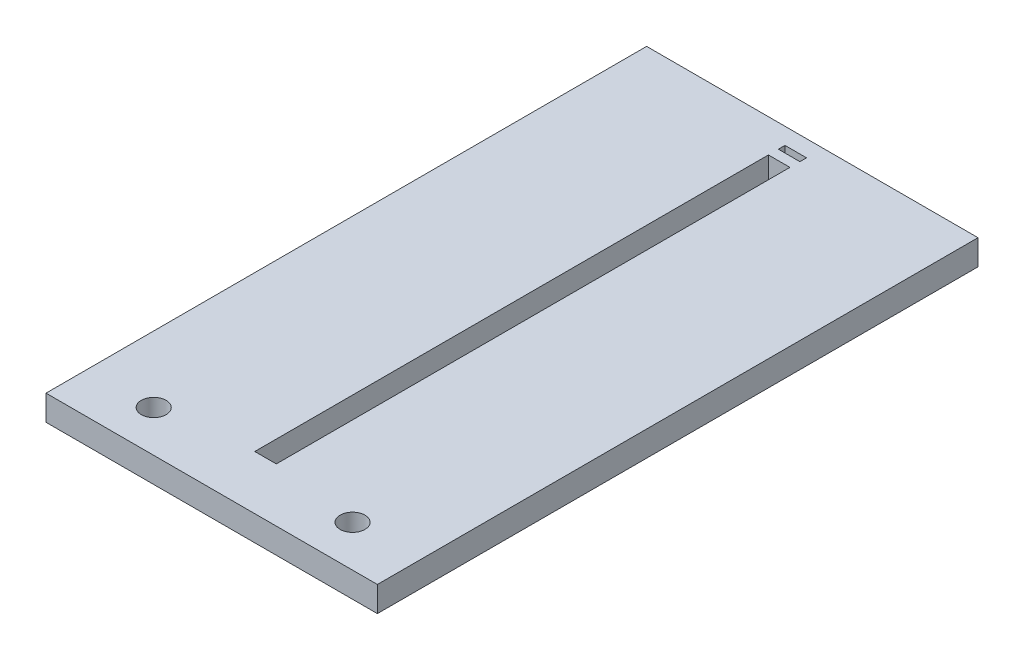
SolidWorks part; units mm, degrees
ref_plane "Front Plane" through (0, 0, 0) normal (0, 0, 1) x (1, 0, 0)
ref_plane "Top Plane" through (0, 0, 0) normal (0, 1, 0) x (1, 0, 0)
ref_plane "Right Plane" through (0, 0, 0) normal (1, 0, 0) x (0, 0, -1)
sketch "Sketch1" plane through (0, 0, 0) normal (0, 1, 0) x (1, 0, 0)
  line L1 (-20, 0) -> (20, 0)
  line L2 (-20, 0) -> (-20, 72.5)
  line L3 (-20, 72.5) -> (20, 72.5)
  line L4 (20, 0) -> (20, 72.5)
  point P5 (0, 0)
  dimension "D1" = 40
  dimension "D2" = 72.5
extrude "Boss-Extrude1" add sketch "Sketch1" along normal blind 3.05 contours L2 | L1 L4 L3 L2 | L4 region at (0, 0, -36.25)
sketch "Sketch4" plane through (0, 3.05, 0) normal (0, 1, 0) x (1, 0, 0)
  line L0 (-20, 72.5) -> (20, 72.5) construction
  line L2 (-20, 0) -> (20, 0) construction
  line L3 (1.3, 70.5) -> (-1.3, 70.5)
  line L4 (-1.3, 70.5) -> (-1.3, 69.7)
  line L5 (-1.3, 69.7) -> (1.3, 69.7)
  line L6 (1.3, 69.7) -> (1.3, 70.5)
  line L7 (0, 0) -> (0, 72.5) construction
  line L9 (1.3, 68.5) -> (-1.3, 68.5)
  line L10 (-1.3, 68.5) -> (-1.3, 6.5)
  line L11 (-1.3, 6.5) -> (1.3, 6.5)
  line L12 (1.3, 6.5) -> (1.3, 68.5)
  point P6 (0, 6.5)
  point P10 (0, 70.5)
  point P22 (0, 68.5)
  dimension "D1" = 2
  dimension "D2" = 0.8
  dimension "D3" = 1.2
  dimension "D4" = 2.6
  dimension "D7" = 6.5
extrude "Cut-Extrude1" cut sketch "Sketch4" against normal through all contours L5 L7 L3 L4 | L11 L7 L9 L10 | L7 L11 L12 L9 | L7 L5 L6 L3 | L6 L3 L4 L5 region at (0.65, 3.05, -70.1) region at (0.65, 3.05, -37.5) region at (-0.65, 3.05, -37.5) region at (-0.65, 3.05, -70.1)
sketch "Sketch7" plane through (0, 3.05, 0) normal (0, 1, 0) x (1, 0, 0)
  line L0 (0, 0) -> (-12, 0)
  line L1 (-20, 0) -> (20, 0) construction
  line L2 (-12, 0) -> (-12, 5)
  line L4 (0, 0) -> (0, 70) construction
  circle A0 centre (-12, 5) radius 1.5
  circle A2 centre (12, 5) radius 1.5
  dimension "D3" = 3
  dimension "D1" = 12
  dimension "D2" = 5
extrude "Cut-Extrude4" cut sketch "Sketch7" against normal through all contours A0 L2 | L2 A0 | A2 region at (-10.9693, 3.05, -3.9693)
